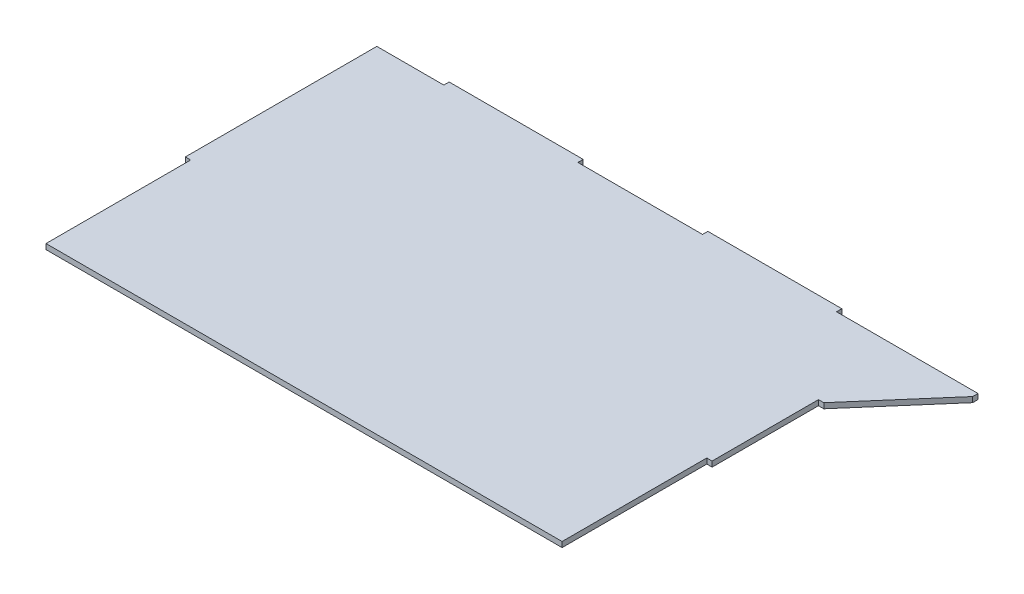
SolidWorks part; units mm, degrees
material "6061-T6 (SS)"
ref_plane "X-Y Datum" through (0, 0, 0) normal (0, 0, 1) x (1, 0, 0)
ref_plane "X-Z Datum" through (0, 0, 0) normal (0, 1, 0) x (1, 0, 0)
ref_plane "Y-Z Datum" through (0, 0, 0) normal (1, 0, 0) x (0, 0, -1)
sketch "Sketch1" plane through (0, 0, 0) normal (0, 0, 1) x (1, 0, 0)
  line L1 (-157.2158, -1.5875) -> (157.2158, -1.5875)
  line L2 (-157.2158, -1.5875) -> (-157.2158, 1.5875)
  line L3 (-157.2158, 1.5875) -> (157.2158, 1.5875)
  line L4 (157.2158, -1.5875) -> (157.2158, 1.5875)
  line L5 (-157.2158, -1.5875) -> (157.2158, 1.5875) construction
  line L6 (-157.2158, 1.5875) -> (157.2158, -1.5875) construction
  point P0 (0, 0)
  dimension "D1" = 314.4317
  dimension "D2" = 3.175
extrude "Boss-Extrude1" add sketch "Sketch1" along normal blind 200.6618
sketch "Sketch3" plane through (0, 0, 0) normal (0, 0, -1) x (-1, 0, 0)
  line L0 (-157.2158, 0) -> (-77.2158, 0) construction
  line L1 (-157.2158, -1.5875) -> (-157.2158, 1.5875) construction
  line L2 (-157.2158, 1.5875) -> (157.2158, 1.5875) construction
  line L3 (-117.2158, -1.5875) -> (-37.2158, -1.5875)
  line L4 (-117.2158, -1.5875) -> (-117.2158, 1.5875)
  line L5 (-117.2158, 1.5875) -> (-37.2158, 1.5875)
  line L6 (-37.2158, -1.5875) -> (-37.2158, 1.5875)
  line L7 (-117.2158, -1.5875) -> (-37.2158, 1.5875) construction
  line L8 (-117.2158, 1.5875) -> (-37.2158, -1.5875) construction
  line L14 (-157.2158, 1.5875) -> (-117.2158, 1.5875)
  line L15 (-157.2158, 1.5875) -> (-157.2158, -1.5875)
  line L16 (-157.2158, -1.5875) -> (-117.2158, -1.5875)
  line L17 (-117.2158, 1.5875) -> (-117.2158, -1.5875)
  line L19 (-37.2158, 1.5875) -> (-37.2158, -1.5875)
  dimension "D1" = 40
  dimension "D2" = 80
sketch "Sketch5" plane through (0, 1.5875, 0) normal (0, 1, 0) x (1, 0, 0)
  line L1 (-157.2158, -200.6618) -> (-154.0408, -200.6618)
  line L3 (-157.2158, -200.6618) -> (-157.2158, -114.3018)
  line L5 (-157.2158, -114.3018) -> (-154.0408, -114.3018)
  line L6 (-154.0408, -200.6618) -> (-154.0408, -114.3018)
  line M11 (-157.2158, 0) -> (-157.2158, -200.6618)
  line M12 (-157.2158, -200.6618) -> (157.2158, -200.6618)
  dimension "D1" = 86.36
  dimension "D2" = 3.175
extrude "Cut-Extrude2" cut sketch "Sketch5" against normal blind 3.175 and the other way through all contours M12 M11 region at (-155.6283, 1.5875, 157.4818)
mirror "Mirror1" about plane through (0, 0, 0) normal (1, 0, 0) of "Cut-Extrude2"
sketch "Sketch6" plane through (0, 1.5875, 0) normal (0, 1, 0) x (1, 0, 0)
  line L6 (-157.2158, -180.3418) -> (-81.0158, -180.3418)
  line L7 (-157.2158, -180.3418) -> (-157.2158, -200.6618)
  line L8 (-157.2158, -200.6618) -> (-81.0158, -200.6618)
  line L9 (-81.0158, -180.3418) -> (-81.0158, -200.6618)
  line L10 (154.0408, -200.6618) -> (-154.0408, -200.6618) construction
  line L11 (-157.2158, -114.3018) -> (-157.2158, 0) construction
  line L13 (154.0408, -200.6618) -> (-81.0158, -200.6618)
  line L14 (154.0408, -200.6618) -> (154.0408, -180.3418)
  line L15 (154.0408, -180.3418) -> (-81.0158, -180.3418)
  line L16 (-81.0158, -200.6618) -> (-81.0158, -180.3418)
  dimension "D1" = 76.2
  dimension "D2" = 20.32
extrude "Cut-Extrude4" [suppressed] cut sketch "Sketch6" against normal through all
sketch "Sketch7" [suppressed] plane through (0, 1.5875, 0) normal (0, 1, 0) x (1, 0, 0)
  line L1 (-81.2823, -215.455) -> (155.1963, -215.455)
  line L2 (-81.2823, -215.455) -> (-81.2823, -235.775)
  line L3 (-81.2823, -235.775) -> (155.1963, -235.775)
  line L4 (155.1963, -215.455) -> (155.1963, -235.775)
extrude "Cut-Extrude5" [suppressed] cut sketch "Sketch7" against normal through all
sketch "Sketch8" [suppressed] plane through (0, 1.5875, 0) normal (0, 1, 0) x (1, 0, 0)
  line L0 (155.1963, -235.775) -> (-155.1963, -235.775) construction
  line L1 (157.4823, -215.455) -> (81.2823, -215.455)
  line L2 (157.4823, -215.455) -> (157.4823, -235.775)
  line L3 (157.4823, -235.775) -> (81.2823, -235.775)
  line L4 (81.2823, -215.455) -> (81.2823, -235.775)
  line L5 (157.4823, -117.411) -> (157.4823, -3.175) construction
  dimension "D1" = 20.32
  dimension "D2" = 76.2
extrude "Cut-Extrude6" [suppressed] cut sketch "Sketch8" against normal through all
sketch "Sketch9" [suppressed] plane through (0, 0, 215.455) normal (0, 0, 1) x (1, 0, 0)
  line L4 (155.1963, 1.5875) -> (-155.1963, 1.5875)
  line L5 (-155.1963, 1.5875) -> (-155.1963, -1.5875)
  line L6 (-155.1963, -1.5875) -> (155.1963, -1.5875)
  line L7 (155.1963, -1.5875) -> (155.1963, 1.5875)
  line L8 (155.1963, 1.5875) -> (-155.1963, 1.5875)
  line L9 (-155.1963, 1.5875) -> (-155.1963, -1.5875)
  line L10 (-155.1963, -1.5875) -> (155.1963, -1.5875)
  line L11 (155.1963, -1.5875) -> (155.1963, 1.5875)
  dimension "D1" = 0
extrude "Cut-Extrude7" [suppressed] cut sketch "Sketch9" against normal blind 11.68
extrude "Boss-Extrude2" add sketch "Sketch3" along normal blind 3.175 contours L6 L4 region at (77.2158, 0, 0)
pattern_linear "LPattern2" count 2 spacing 154.43 along (-1, 0, 0) of "Boss-Extrude2"
sketch "Sketch10" plane through (0, -1.5875, 0) normal (0, -1, 0) x (1, 0, 0)
  line L2 (201.6506, 0) -> (201.6506, 3.175)
  line L8 (157.2158, 0) -> (201.6506, 0)
  line L10 (157.2158, 114.3018) -> (157.2158, 0) construction
  line L11 (157.2158, 50.8) -> (157.2158, 0)
  line L12 (157.2158, 50.8) -> (160.3908, 50.8)
  line L13 (160.3908, 50.8) -> (201.6506, 3.175)
  dimension "D1" = 50.8
  dimension "D2" = 44.4348
  dimension "D3" = 3.175
  dimension "D4" = 3.175
extrude "Boss-Extrude3" add sketch "Sketch10" against normal blind 3.175
sketch "Sketch11" [suppressed] plane through (0, 0, 0) normal (0, 0, -1) x (-1, 0, 0)
  line L1 (37.2652, -1.5875) -> (117.2652, -1.5875)
  line L2 (37.2652, -1.5875) -> (37.2652, 1.5875)
  line L3 (37.2652, 1.5875) -> (117.2652, 1.5875)
  line L4 (117.2652, -1.5875) -> (117.2652, 1.5875)
  line L5 (-117.1668, -1.5875) -> (-37.1668, -1.5875)
  line L6 (-117.1668, -1.5875) -> (-117.1668, 1.5875)
  line L7 (-117.1668, 1.5875) -> (-37.1668, 1.5875)
  line L8 (-37.1668, -1.5875) -> (-37.1668, 1.5875)
extrude "Boss-Extrude4" [suppressed] add sketch "Sketch11" along normal blind 3.175
